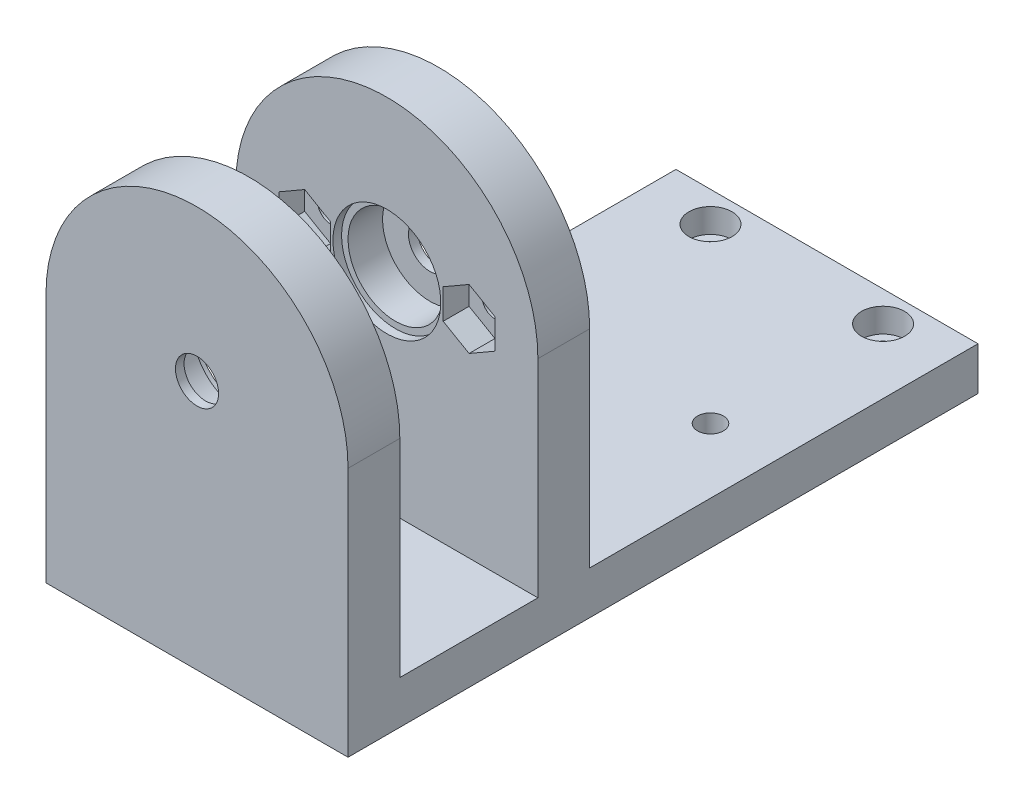
SolidWorks part; units mm, degrees
ref_plane "Front Plane" through (0, 0, 0) normal (0, 0, 1) x (1, 0, 0)
ref_plane "Top Plane" through (0, 0, 0) normal (0, 1, 0) x (1, 0, 0)
ref_plane "Right Plane" through (0, 0, 0) normal (1, 0, 0) x (0, 0, -1)
sketch "Sketch1" plane through (0, 0, 0) normal (0, 1, 0) x (1, 0, 0)
  line L0 (-27.381, 0) -> (53.0952, 0) construction
  line L1 (0, 33.6905) -> (0, -17.5) construction
  line L2 (-10, 20) -> (10, 20) construction
  line L3 (-10, 10) -> (10, 10) construction
  line L4 (-10, 10) -> (-10, 30) construction
  line L5 (-10, 30) -> (10, 30) construction
  line L6 (10, 10) -> (10, 30) construction
  line L7 (-10, 10) -> (10, 30) construction
  line L8 (-10, 30) -> (10, 10) construction
  line L9 (-10, -30) -> (10, -30) construction
  line L10 (-10, -30) -> (10, -10) construction
  line L11 (-10, -20) -> (10, -20) construction
  line L12 (-10, -10) -> (-10, -30) construction
  line L13 (-10, -10) -> (10, -30) construction
  line L14 (-10, -10) -> (10, -10) construction
  line L15 (10, -10) -> (10, -30) construction
  line L16 (-17.5, -33.5) -> (17.5, -6.5) construction
  line L17 (-17.5, 6.5) -> (17.5, 6.5) construction
  line L18 (-17.5, 6.5) -> (-17.5, 33.5) construction
  line L19 (-17.5, 33.5) -> (17.5, 33.5) construction
  line L20 (17.5, 6.5) -> (17.5, 33.5) construction
  line L21 (-17.5, 6.5) -> (17.5, 33.5) construction
  line L22 (-17.5, 33.5) -> (17.5, 6.5) construction
  line L23 (-17.5, -6.5) -> (-17.5, -33.5) construction
  line L24 (-17.5, -33.5) -> (17.5, -33.5) construction
  line L25 (17.5, -6.5) -> (17.5, -33.5) construction
  line L26 (-17.5, -6.5) -> (17.5, -6.5) construction
  line L27 (-17.5, -6.5) -> (17.5, -33.5) construction
  line L28 (-17.5, 33.5) -> (17.5, 33.5)
  line L32 (17.5, 33.5) -> (17.5, -39.5)
  line L33 (-17.5, 33.5) -> (-17.5, -39.5)
  line L34 (-17.5, -39.5) -> (17.5, -39.5)
  circle A0 centre (-10, 30) radius 1.5
  circle A1 centre (10, 30) radius 1.5
  circle A2 centre (10, 10) radius 1.5
  circle A3 centre (-10, 10) radius 1.5
  circle A4 centre (-10, -10) radius 1.5 construction
  circle A5 centre (10, -10) radius 1.5 construction
  circle A6 centre (10, -30) radius 1.5
  circle A7 centre (-10, -30) radius 1.5
  point P4 (0, 20)
  point P26 (0, 20)
  dimension "D3" = 3
  dimension "D1" = 20
  dimension "D2" = 40
  dimension "D4" = 35
  dimension "D5" = 27
  dimension "D6" = 6
extrude "Boss-Extrude1" add sketch "Sketch1" along normal blind 5
sketch "Sketch2" plane through (0, 5, 0) normal (0, 1, 0) x (1, 0, 0)
  circle A0 centre (-10, 30) radius 2.5
  circle A1 centre (10, 30) radius 2.5
  circle A9 centre (-10, -30) radius 2.5
  circle A10 centre (10, -30) radius 2.5
  dimension "D1" = 5
extrude "Cut-Extrude1" cut sketch "Sketch2" against normal blind 2.8
ref_plane "Plane1" through (0, 0, 33.5) normal (0, 0, 1) x (1, 0, 0)
sketch "Sketch3" plane through (0, 0, 33.5) normal (0, 0, 1) x (1, 0, 0)
  line L0 (-17.5, 5) -> (17.5, 5)
  line L1 (17.5, 5) -> (17.5, 29)
  line L2 (-17.5, 5) -> (-17.5, 29)
  arc A0 (-17.5, 29) -> (17.5, 29) centre (0, 29) cw
  circle A1 centre (0, 29) radius 2.5
  point P8 (0, 0)
  point P9 (0, 0)
  point P10 (0, 0)
  point P11 (-22.7, 5)
  point P12 (-22.5447, 9.3653)
  point P13 (-20.0923, 9.9258)
  point P14 (0, 0)
  point P16 (0, 0)
  point P17 (0, 0)
  dimension "D1" = 5
  dimension "D2" = 24
extrude "Boss-Extrude2" add sketch "Sketch3" along normal blind 6
sketch "Sketch4" plane through (0, 0, 33.5) normal (0, 0, -1) x (-1, 0, 0)
  circle A0 centre (0, 29) radius 6.25
  dimension "D1" = 12.5
extrude "Cut-Extrude2" cut sketch "Sketch4" against normal blind 1
sketch "Sketch5" plane through (0, 0, 34.5) normal (0, 0, -1) x (-1, 0, 0)
  circle A0 centre (0, 29) radius 5.5
  dimension "D1" = 11
extrude "Cut-Extrude3" cut sketch "Sketch5" against normal blind 4
ref_plane "Mirror Plane" through (0, 0, 25.5) normal (0, 0, 1) x (1, 0, 0)
mirror "Mirror1" about plane through (0, 0, 25.5) normal (0, 0, 1) of "Cut-Extrude3", "Cut-Extrude2", "Boss-Extrude2"
sketch "Sketch6" plane through (0, 0, 11.5) normal (0, 0, -1) x (-1, 0, 0)
  line L0 (-9.525, 29) -> (9.525, 29) construction
  line L1 (0, 38.525) -> (0, 19.475) construction
  circle A0 centre (0, 29) radius 9.525 construction
  circle A1 centre (-9.525, 29) radius 1.5
  circle A2 centre (9.525, 29) radius 1.5
  dimension "D1" = 19.05
  dimension "D2" = 3
extrude "Cut-Extrude4" cut sketch "Sketch6" against normal up to surface (6 mm away) up to face at (-6.25, 29, 17.5)
sketch "Sketch7" plane through (0, 0, 17.5) normal (0, 0, 1) x (1, 0, 0)
  line L0 (0, 0) -> (0, 46.5) construction
  line L1 (-12.525, 30.7321) -> (-12.525, 27.2679)
  line L2 (-12.525, 27.2679) -> (-9.525, 25.5359)
  line L3 (-9.525, 25.5359) -> (-6.525, 27.2679)
  line L4 (-6.525, 27.2679) -> (-6.525, 30.7321)
  line L5 (-6.525, 30.7321) -> (-9.525, 32.4641)
  line L6 (-9.525, 32.4641) -> (-12.525, 30.7321)
  line L7 (9.525, 32.4641) -> (12.525, 30.7321)
  line L8 (6.525, 30.7321) -> (9.525, 32.4641)
  line L9 (6.525, 27.2679) -> (6.525, 30.7321)
  line L10 (9.525, 25.5359) -> (6.525, 27.2679)
  line L11 (12.525, 27.2679) -> (9.525, 25.5359)
  line L12 (12.525, 30.7321) -> (12.525, 27.2679)
  circle A0 centre (-9.525, 29) radius 3 construction
  arc A1 (17.5, 29) -> (-17.5, 29) centre (0, 29) ccw construction
  circle A2 centre (9.525, 29) radius 3 construction
  dimension "D1" = 6
extrude "Cut-Extrude5" cut sketch "Sketch7" against normal blind 3
